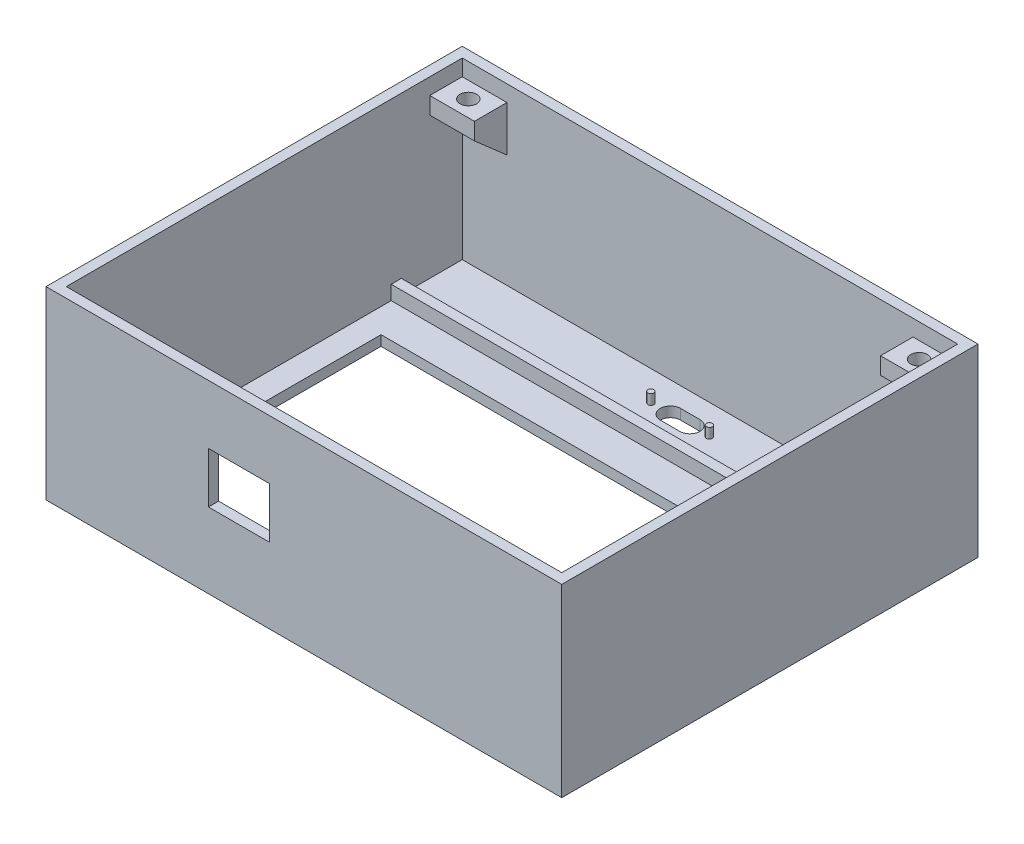
SolidWorks part; units mm, degrees
ref_plane "Front Plane" through (0, 0, 0) normal (0, 0, 1) x (1, 0, 0)
ref_plane "Top Plane" through (0, 0, 0) normal (0, 1, 0) x (1, 0, 0)
ref_plane "Right Plane" through (0, 0, 0) normal (1, 0, 0) x (0, 0, -1)
sketch "Sketch1" plane through (0, 0, 0) normal (0, 1, 0) x (1, 0, 0)
  line L1 (0, 0) -> (127, 0)
  line L2 (0, 0) -> (0, 85)
  line L3 (0, 85) -> (127, 85)
  line L4 (127, 0) -> (127, 85)
extrude "Boss-Extrude1" add sketch "Sketch1" along normal blind 2.5
sketch "Sketch2" plane through (0, 2.5, 0) normal (0, 1, 0) x (1, 0, 0)
  line L0 (0, 85) -> (127, 85)
  line L1 (127, 85) -> (127, 0)
  line L2 (127, 0) -> (0, 0)
  line L3 (0, 0) -> (0, 85)
  line L5 (2.5, 82.5) -> (124.5, 82.5)
  line L6 (2.5, 82.5) -> (2.5, 2.5)
  line L7 (2.5, 2.5) -> (124.5, 2.5)
  line L8 (124.5, 82.5) -> (124.5, 2.5)
  dimension "D1" = 2.5
  dimension "D2" = 2.5
  dimension "D3" = 2.5
  dimension "D4" = 2.5
extrude "Boss-Extrude2" add sketch "Sketch2" along normal blind 38.5
sketch "Sketch3" plane through (0, 0, 0) normal (0, -1, 0) x (-1, 0, 0)
  line L0 (-127, 85) -> (0, 85) construction
  line L1 (-8.5, 5.5) -> (-118.5, 5.5)
  line L2 (-8.5, 5.5) -> (-8.5, 74)
  line L3 (-8.5, 74) -> (-118.5, 74)
  line L4 (-118.5, 5.5) -> (-118.5, 74)
  line L6 (0, 0) -> (-127, 0) construction
  line L7 (-127, 0) -> (-127, 85) construction
  line L8 (0, 85) -> (0, 0) construction
  dimension "D1" = 11
  dimension "D2" = 5.5
  dimension "D3" = 8.5
  dimension "D4" = 8.5
extrude "Cut-Extrude1" cut sketch "Sketch3" against normal blind 2.5
sketch "Sketch6" plane through (0, 0, 0) normal (0, -1, 0) x (-1, 0, 0)
  line L8 (-61.1, 92.6537) -> (-65.9, 92.6537) construction
  line L9 (-61.1, 90.1537) -> (-65.9, 90.1537)
  line L10 (-61.1, 95.1537) -> (-65.9, 95.1537)
  arc A0 (-61.1, 90.1537) -> (-61.1, 95.1537) centre (-61.1, 92.6537) ccw
  arc A2 (-65.9, 95.1537) -> (-65.9, 90.1537) centre (-65.9, 92.6537) ccw
  point P1 (-63.5, 92.6537)
sketch "Sketch9" plane through (0, 0, -85) normal (0, 0, -1) x (-1, 0, 0)
  line L0 (-127, 0) -> (0, 0) construction
  line L1 (-127, 0) -> (0, 0)
  line L2 (-127, 0) -> (-127, 2.5)
  line L4 (0, 0) -> (0, 2.5)
  line L5 (-127, 41) -> (-127, 0) construction
  line L6 (0, 41) -> (0, 0) construction
  line L7 (-2.5, 2.5) -> (-124.5, 2.5)
  line L8 (-127, 41) -> (-124.5, 41)
  line L9 (-127, 41) -> (-127, 2.5)
  line L11 (-124.5, 41) -> (-124.5, 2.5)
  line L12 (0, 41) -> (-2.5, 41)
  line L13 (0, 41) -> (0, 2.5)
  line L15 (-2.5, 41) -> (-2.5, 2.5)
  dimension "D2" = 2.5
  dimension "D3" = 2.5
extrude "Boss-Extrude3" add sketch "Sketch9" along normal blind 15
sketch "Sketch10" plane through (0, 41, 0) normal (0, 1, 0) x (1, 0, 0)
  line L1 (2.5, 85) -> (124.5, 85)
  line L2 (2.5, 85) -> (2.5, 82.5)
  line L3 (2.5, 82.5) -> (124.5, 82.5)
  line L4 (124.5, 85) -> (124.5, 82.5)
extrude "Cut-Extrude2" cut sketch "Sketch10" against normal blind 35
sketch "Sketch11" plane through (0, 0, -100) normal (0, 0, -1) x (-1, 0, 0)
  line L1 (0, 0) -> (-127, 0)
  line L2 (0, 0) -> (0, 41)
  line L3 (0, 41) -> (-127, 41)
  line L4 (-127, 0) -> (-127, 41)
extrude "Boss-Extrude4" add sketch "Sketch11" along normal blind 2.5
sketch "Sketch13" plane through (0, 2.5, 0) normal (0, 1, 0) x (1, 0, 0)
  circle A0 centre (56.3, 92.6537) radius 0.725
  circle A1 centre (70.7, 92.6537) radius 0.725
  arc A2 (61.1, 95.1537) -> (61.1, 90.1537) centre (61.1, 92.6537) ccw construction
  dimension "D1" = 14.4
  dimension "D2" = 4.8
  dimension "D3" = 4.8
  dimension "D4" = 1.45
  dimension "D5" = 1.45
extrude "Cut-Extrude4" cut sketch "Sketch6" against normal blind 2.5
sketch "Sketch14" plane through (0, 2.5, 0) normal (0, 1, 0) x (1, 0, 0)
  line L1 (56, 87.5534) -> (71, 87.5534)
  line L2 (56, 87.5534) -> (56, 85.0723)
  line L3 (56, 85.0723) -> (71, 85.0723)
  line L4 (71, 87.5534) -> (71, 85.0723)
  arc A0 (61.1, 95.1537) -> (61.1, 90.1537) centre (61.1, 92.6537) ccw construction
  arc A1 (65.9, 90.1537) -> (65.9, 95.1537) centre (65.9, 92.6537) ccw construction
  dimension "D1" = 5.1
  dimension "D2" = 5.1
extrude "Cut-Extrude5" cut sketch "Sketch14" against normal blind 1.5
extrude "Boss-Extrude6" add sketch "Sketch13" along normal blind 2.5
sketch "Sketch17" plane through (0, 0, 0) normal (0, 0, 1) x (1, 0, 0)
  line L0 (0, 41) -> (0, 0) construction
  line L1 (40, 31) -> (55, 31)
  line L2 (40, 31) -> (40, 18.5)
  line L3 (40, 18.5) -> (55, 18.5)
  line L4 (55, 31) -> (55, 18.5)
  line L5 (0, 0) -> (127, 0) construction
  dimension "D1" = 40
  dimension "D2" = 18.5
  dimension "D3" = 12.5
  dimension "D4" = 15
extrude "Cut-Extrude6" cut sketch "Sketch17" against normal blind 2.5
sketch "Sketch19" plane through (0, 41, 0) normal (0, 1, 0) x (1, 0, 0)
  line L0 (0, 102.5) -> (127, 102.5)
  line L1 (127, 102.5) -> (127, 0)
  line L2 (127, 0) -> (0, 0)
  line L3 (0, 0) -> (0, 102.5)
  line L5 (2.5, 100) -> (124.5, 100)
  line L6 (2.5, 100) -> (2.5, 2.5)
  line L7 (2.5, 2.5) -> (124.5, 2.5)
  line L8 (124.5, 100) -> (124.5, 2.5)
extrude "Boss-Extrude7" add sketch "Sketch19" along normal blind 4.5
sketch "Sketch20" plane through (0, 0, -100) normal (0, 0, 1) x (1, 0, 0)
  line L0 (2.5, 45.5) -> (2.5, 2.5) construction
  line L1 (2.5, 41.5) -> (13.5, 41.5)
  line L2 (2.5, 41.5) -> (2.5, 37.3158)
  line L3 (2.5, 37.3158) -> (13.5, 37.3158)
  line L4 (13.5, 41.5) -> (13.5, 37.3158)
  line L5 (124.5, 45.5) -> (2.5, 45.5) construction
  line L6 (113.5, 37.3158) -> (124.5, 37.3158)
  line L7 (113.5, 41.5) -> (113.5, 37.3158)
  line L8 (113.5, 41.5) -> (124.5, 41.5)
  line L9 (124.5, 41.5) -> (124.5, 37.3158)
  dimension "D1" = 4
  dimension "D2" = 11
extrude "Boss-Extrude8" add sketch "Sketch20" along normal blind 8
sketch "Sketch22" plane through (0, 41.5, 0) normal (0, 1, 0) x (1, 0, 0)
  line L0 (124.5, 2.5) -> (124.5, 100) construction
  line L2 (2.5, 92) -> (2.5, 100) construction
  line L5 (13.5, 100) -> (2.5, 100) construction
  circle A0 centre (8, 96) radius 2.05
  circle A1 centre (119, 96) radius 2.05
  dimension "D1" = 4
  dimension "D2" = 5.5
  dimension "D4" = 5.5
  dimension "D5" = 4.1
  dimension "D3" = 2
extrude "Cut-Extrude7" cut sketch "Sketch22" against normal blind 5
sketch "Sketch23" plane through (2.5, 0, 0) normal (1, 0, 0) x (0, 0, -1)
  line L0 (92, 37.3158) -> (100, 37.3158)
  line L1 (100, 37.3158) -> (100, 2.5) construction
  line L2 (100, 37.3158) -> (100, 30.3158)
  line L3 (100, 30.3158) -> (92, 37.3158)
  dimension "D1" = 7
extrude "Boss-Extrude9" add sketch "Sketch23" along normal blind 11
sketch "Sketch24" plane through (124.5, 0, 0) normal (-1, 0, 0) x (0, 0, 1)
  line L3 (-92, 37.3158) -> (-100, 37.3158)
  line L4 (-92, 37.3158) -> (-100, 37.3158) construction
  line L5 (-100, 37.3158) -> (-100, 30.3158)
  line L6 (-100, 2.5) -> (-100, 37.3158) construction
  line L7 (-100, 30.3158) -> (-92, 37.3158)
  dimension "D1" = 7
extrude "Boss-Extrude10" add sketch "Sketch24" along normal blind 11
